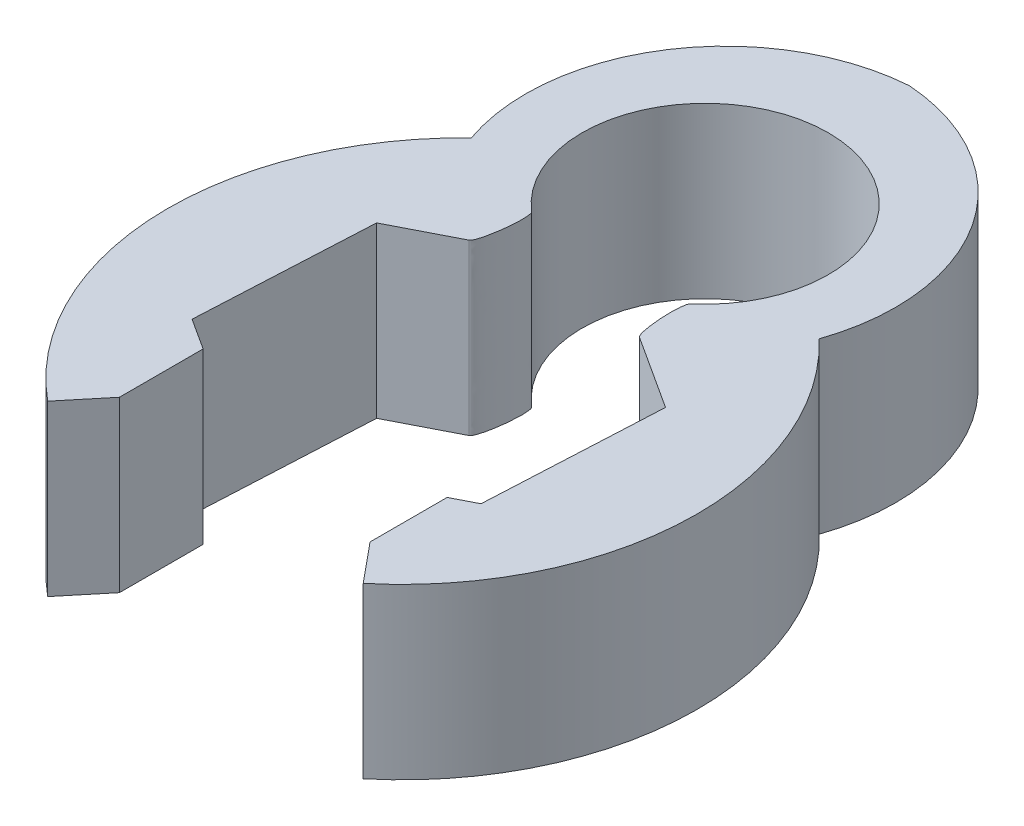
SolidWorks part; units mm, degrees
ref_plane "Front Plane" through (0, 0, 0) normal (0, 0, 1) x (1, 0, 0)
ref_plane "Top Plane" through (0, 0, 0) normal (0, 1, 0) x (1, 0, 0)
ref_plane "Right Plane" through (0, 0, 0) normal (1, 0, 0) x (0, 0, -1)
sketch "Sketch3" plane through (0, 0, 0) normal (0, 1, 0) x (1, 0, 0)
  line L0 (-7.2765, 0.1114) -> (11.8281, 0.1114) construction
  line L1 (-2.4796, 5.151) -> (-2.4796, 6.4742)
  line L2 (5.874, 3.0075) -> (0.3324, 6.5907)
  line L3 (0.3324, 6.5907) -> (-5.5415, 3.5833)
  line L4 (-5.5415, 3.5833) -> (-5.874, -3.0075)
  line L5 (-5.874, -3.0075) -> (-0.3324, -6.5907)
  line L6 (-0.3324, -6.5907) -> (5.5415, -3.5833)
  line L7 (5.5415, -3.5833) -> (5.874, 3.0075)
  line L8 (2.4796, 5.151) -> (2.4796, 6.4742)
  line L9 (-4.7012, -3.7658) -> (-4.7012, -6.9056)
  line L10 (-4.7012, -6.9056) -> (-5.9188, -8.3785)
  line L11 (0, 2.9063) -> (0, -1.8101) construction
  line L12 (4.7012, -6.9056) -> (5.9188, -8.3785)
  line L13 (4.7012, -3.7658) -> (4.7012, -6.9056)
  circle A0 centre (0, 0) radius 5.715 construction
  circle A1 centre (0, 10.3692) radius 4.6174
  arc A2 (-5.9188, -8.3785) -> (-6.5266, 8.121) centre (1.1246, 0.1419) cw
  arc A3 (-6.5266, 8.121) -> (0, 18.035) centre (0.5425, 10.5725) cw
  arc A4 (6.5266, 8.121) -> (0, 18.035) centre (-0.5425, 10.5725) ccw
  arc A5 (5.9188, -8.3785) -> (6.5266, 8.121) centre (-1.1246, 0.1419) ccw
  dimension "D1" = 11.43
  dimension "D2" = 0
extrude "Boss-Extrude1" add sketch "Sketch3" along normal blind 6.35 contours L12 A5 A4 A3 A2 L10 L9 L5 L4 L3 L1 A1 L8 L2 L7 L6 L13 | A1 L1 L3 | A1 L2 L8 region at (-4.1612, 0, -4.6613) region at (-2.0247, 0, -5.8096) region at (2.1055, 0, -5.8575)
fillet "Fillet6" radius 1.27 2 edges at (1.328, 3.175, -5.947) (-1.0635, 3.175, -5.876) conic radius 6.35
sketch "Sketch4" plane through (0, 6.35, 0) normal (0, 1, 0) x (1, 0, 0)
  line L1 (-6.1573, 3.9814) -> (-6.5266, -3.3416)
  line L2 (-6.5266, -3.3416) -> (-0.3694, -7.323)
  line L3 (-0.3694, -7.323) -> (6.1573, -3.9814)
  line L4 (6.1573, -3.9814) -> (6.5266, 3.3416)
  line L5 (6.5266, 3.3416) -> (0.3694, 7.323)
  line L6 (0.3694, 7.323) -> (-6.1573, 3.9814)
  circle A0 centre (0, 0) radius 6.35 construction
